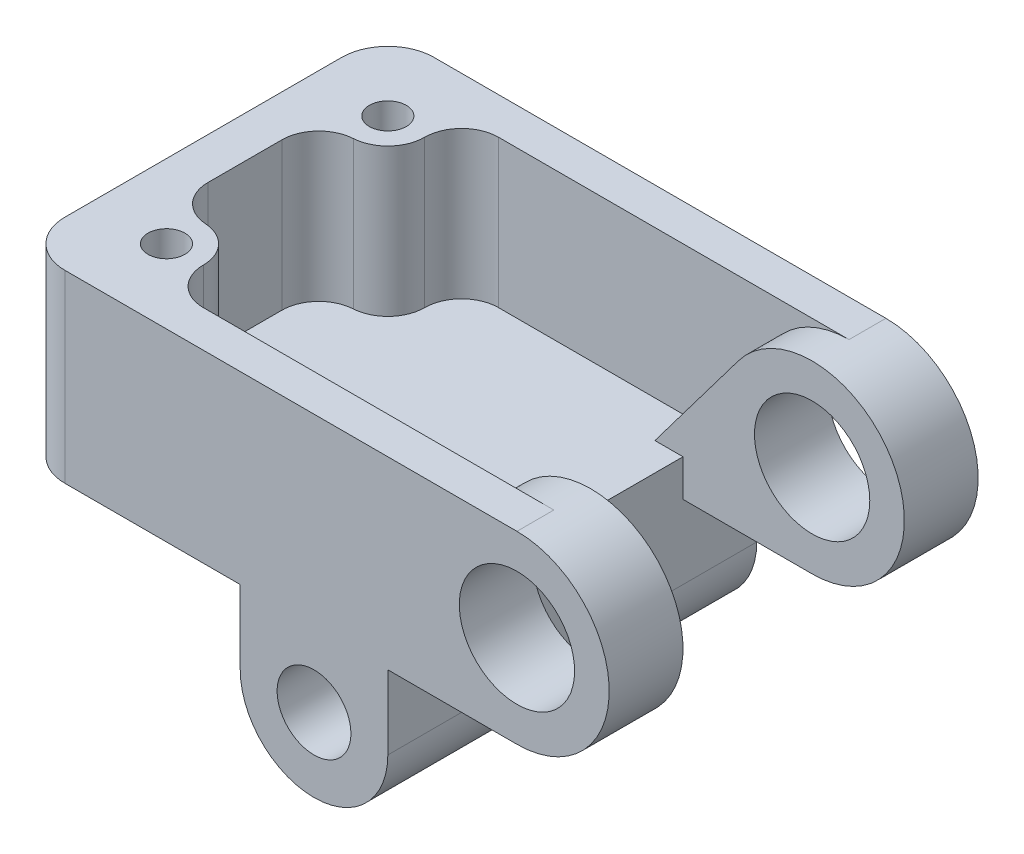
SolidWorks part; units mm, degrees
ref_plane "Front Plane" through (0, 0, 0) normal (0, 0, 1) x (1, 0, 0)
ref_plane "Top Plane" through (0, 0, 0) normal (0, 1, 0) x (1, 0, 0)
ref_plane "Right Plane" through (0, 0, 0) normal (1, 0, 0) x (0, 0, -1)
sketch "Sketch1" plane through (0, 0, 0) normal (0, 0, 1) x (1, 0, 0)
  line L0 (0, 0) -> (-74.4012, 0) construction
  line L1 (0, 0) -> (0, -9.5179) construction
  line L2 (9, 0) -> (48, 0)
  line L3 (0, 0) -> (9, 0)
  line L4 (0, 0) -> (0, 40)
  line L5 (0, 40) -> (9, 40)
  line L6 (9, 8) -> (9, 40)
  line L7 (0, 0) -> (-8, 0)
  line L8 (0, 0) -> (0, 32)
  line L9 (0, 32) -> (-8, 32)
  line L10 (-8, 0) -> (-8, 32)
  line L11 (9, 8) -> (80, 8)
  line L12 (80, -16) -> (80, 8)
  line L13 (48, -16) -> (48, 0)
  line L14 (9, 40) -> (108, 40)
  line L15 (92.0273, 32.0363) -> (73.9146, 8)
  line L16 (108, 0) -> (80, 0)
  line L17 (48, 0) -> (80, 0)
  line L18 (9, 8) -> (9, 0)
  arc A0 (48, -16) -> (80, -16) centre (64, -16) ccw
  circle A1 centre (64, -16) radius 8
  arc A2 (108, 0) -> (92.0273, 32.0363) centre (108, 20) ccw
  circle A3 centre (108, 20) radius 12.5
  dimension "D5" = 72
  dimension "D7" = 32
  dimension "D8" = 16
  dimension "D10" = 44
  dimension "D11" = 40
  dimension "D12" = 25
  dimension "D1" = 40
  dimension "D2" = 9
  dimension "D3" = 32
  dimension "D4" = 8
  dimension "D6" = 16
  dimension "D9" = 8
  dimension "D13" = 53
extrude "Boss-Extrude1" add sketch "Sketch1" against normal blind 16 contours A2 L15 L11 L12 L16 A3 region at (80.6727, 4, 0)
extrude "Boss-Extrude2" add sketch "Sketch1<5>" against normal blind 8 contours A2 L14 L6 L11 L15 region at (48.0978, 24.9141, 0)
sketch "Sketch1<5>" plane through (0, 0, 0) normal (0, 0, 1) x (1, 0, 0) same geometry as "Sketch1"
extrude "Boss-Extrude3" add sketch "Sketch1<6>" against normal blind 80 contours L18 L6 L5 L4 L3 | L11 L18 L2 L17 L12 | L13 A0 L12 L17 A1 region at (44.5, 4, 0) region at (4.5, 20, 0) region at (64, -0.4525, 0)
sketch "Sketch1<6>" plane through (0, 0, 0) normal (0, 0, 1) x (1, 0, 0) same geometry as "Sketch1"
ref_plane "Plane1" through (0, 0, -40) normal (0, 0, 1) x (1, 0, 0)
mirror "Mirror1" about plane through (0, 0, -40) normal (0, 0, 1) of "Boss-Extrude2", "Boss-Extrude1"
extrude "Boss-Extrude4" add sketch "Sketch1<7>" against normal blind 32 from offset 24 contours L10 L7 L4 L9 region at (-4, 16, 0) offset against normal yes
sketch "Sketch1<7>" plane through (0, 0, 0) normal (0, 0, 1) x (1, 0, 0) same geometry as "Sketch1"
fillet "Fillet1" 2 edges at (-4, 32, -56) (-4, 32, -24) type full round first side face at (-4, 16, -56) second side face at (-4, 16, -24) middle face at (-4, 32, -40)
hole_wizard "Ø8.0mm Dowel Hole1" positions "3DSketch1" profile "Sketch2" hole size "Ø8.0" standard "ANSI Metric"
sketch3d "3DSketch1"
  line L0 (0, 16, -40) -> (-8, 16, -40) construction
  point P0 (-8, 16, -40)
sketch "Sketch2" plane through (-8, 16, -40) normal (0, 1, 0) x (0, 0, 1)
  line L0 (0, 0) -> (0, 8)
  line L1 (0, 8) -> (4, 8)
  line L2 (4, 8) -> (4, 0)
  line L5 (4, 0) -> (0, 0)
  line L10 (0, 8) -> (-4, 8) construction
  line L11 (0, -6.35) -> (0, 107.95) construction
  dimension "Hole Dia." = 8
  dimension "Hole Depth" = 8
  dimension "Drill Angle" = 180
sketch "Sketch3" plane through (0, 40, 0) normal (0, 1, 0) x (1, 0, 0)
  line L1 (0, 80) -> (0, 0) construction
  line L2 (9, 72) -> (32, 72)
  line L3 (0, 40) -> (63.6628, 40) construction
  line L4 (9, 72) -> (73.9146, 72) construction
  line L5 (9, 72) -> (9, 8) construction
  line L6 (9, 48.0313) -> (9, 72)
  line L7 (9, 8) -> (32, 8)
  line L8 (9, 31.9687) -> (9, 8)
  circle A0 centre (16, 64) radius 4
  circle A1 centre (16, 16) radius 4
  arc A2 (16.5, 56.0156) -> (24, 64) centre (16, 64) ccw
  arc A3 (32, 72) -> (24, 64) centre (32, 64) ccw
  arc A4 (16.5, 56.0156) -> (9, 48.0313) centre (17, 48.0313) ccw
  circle A5 centre (16, 16) radius 4
  arc A6 (16.5, 23.9844) -> (9, 31.9687) centre (17, 31.9687) cw
  arc A7 (16.5, 23.9844) -> (24, 16) centre (16, 16) cw
  arc A8 (32, 8) -> (24, 16) centre (32, 16) cw
  point P30 (-142.5111, 68.9774)
  line M11 (108, 8) -> (9, 8)
  line M12 (9, 8) -> (9, 72)
  line M13 (9, 72) -> (108, 72)
  dimension "D1" = 8
  dimension "D5" = 16
  dimension "D3" = 16
  dimension "D4" = 48
extrude "Boss-Extrude5" add sketch "Sketch3" against normal up to next contours A4 A2 A3 A0 M13 M12 | A8 A7 A6 A1 M11 M12 region at (10.9269, 40, -26.2641) region at (20.5, 40, -71.6678)
fillet "Fillet2" radius 10 2 edges at (0, 20, -80) (0, 20, 0)
